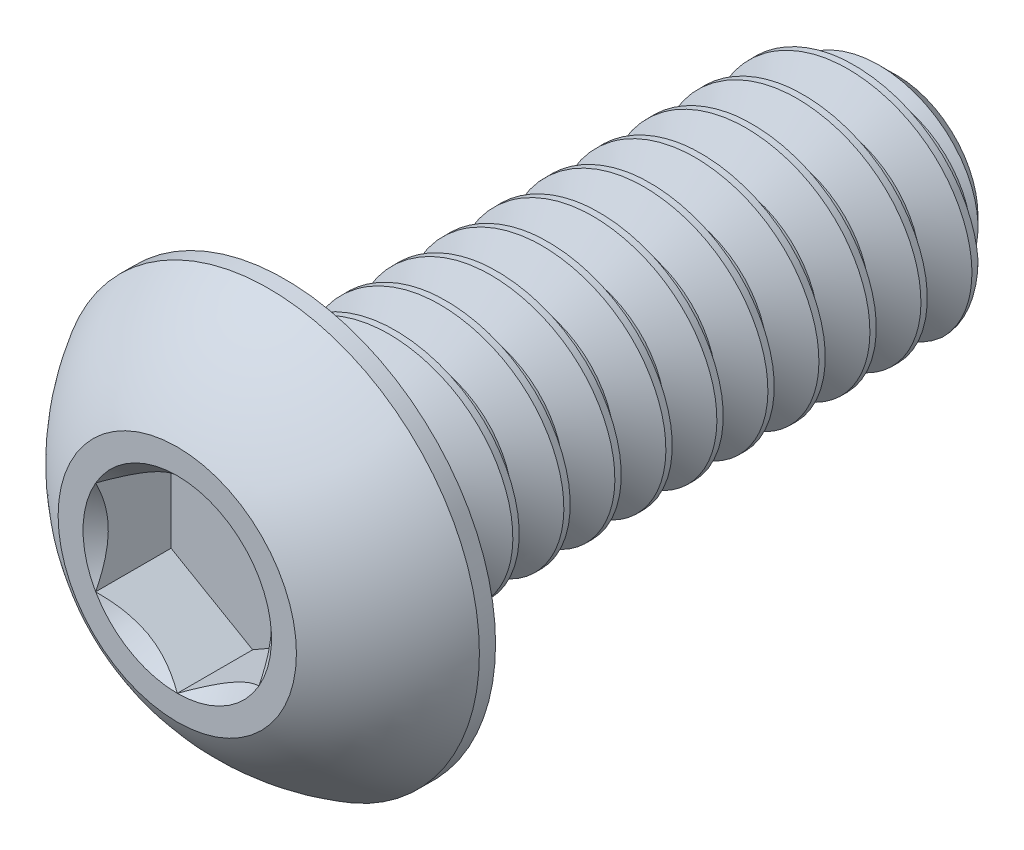
SolidWorks part; units mm, degrees
ref_plane "Front" through (0, 0, 0) normal (0, 0, 1) x (1, 0, 0)
ref_plane "Top" through (0, 0, 0) normal (0, 1, 0) x (1, 0, 0)
ref_plane "Right" through (0, 0, 0) normal (1, 0, 0) x (0, 0, -1)
sketch "Sketch1" plane through (0, 0, 0) normal (1, 0, 0) x (0, 0, -1)
  line L2 (0.8382, 0.9271) -> (5.6007, 0.9271)
  line L3 (5.6007, 0.9271) -> (5.6007, 0)
  line L4 (5.6007, 0) -> (0.8382, 0)
  line L6 (0.7125, 1.6383) -> (0.8382, 1.6383) construction
  line L7 (5.6007, 0.9271) -> (5.6007, -0.9271) construction
  line L8 (0, 0) -> (0.8382, 0) construction
  line L9 (0.8382, 1.6383) -> (0.8382, -1.6383) construction
  line L11 (0.8382, 0.9271) -> (0.8382, 0)
  line L13 (0, 0.635) -> (0, -0.635) construction
  line L14 (0, 0.635) -> (0, 0.9271) construction
  arc A3 (0, 0.9271) -> (0.7125, 1.6383) centre (1.6366, 0) cw construction
  dimension "D1" = 0.1257
revolve "Revolve1" add sketch "Sketch1" angle 360 mid plane about L4
sketch "Sketch3" plane through (0, 0, -5.6007) normal (0, 0, -1) x (-1, 0, 0)
  circle A0 centre (0, 0) radius 0.9271
curve "Helix/Spiral1" pitch 0.3969 height 5.1594 radius 0.9271 centre (0, 0, -5.6007) axis (0, 0, 1) start towards (0, 1, 0)
sketch "Sketch2" plane through (0, 0, 0) normal (1, 0, 0) x (0, 0, -1)
  line L0 (5.6007, 0.9271) -> (5.948, 0.9271)
  line L1 (5.948, 0.9271) -> (5.7991, 0.6693)
  line L2 (5.7991, 0.6693) -> (5.7495, 0.6693)
  line L3 (5.7495, 0.6693) -> (5.6007, 0.9271)
  line L4 (5.6751, 0.7982) -> (5.8736, 0.7982) construction
  dimension "D1" = 60
  dimension "D2" = 0.0496
  dimension "D3" = 0.1984
chamfer "Chamfer1" distance 0.2977 angle 45 1 edges at (0, 0.9271, -5.6007)
sweep "Cut-Sweep1" cut profiles "Sketch2" path "Helix/Spiral1"
sketch "Sketch7" plane through (0, 0, 0) normal (1, 0, 0) x (0, 0, -1)
  line L6 (0.7125, 1.6383) -> (0.8382, 1.6383) construction
  line L8 (0, 0) -> (0.8382, 0) construction
  line L11 (0.8382, 1.6383) -> (0.8382, -1.6383) construction
  line L12 (0.7125, 1.6383) -> (0.8382, 1.6383)
  line L13 (0, 0) -> (0.8382, 0)
  line L14 (0, 0.635) -> (0, -0.635) construction
  line L15 (0.8382, 1.6383) -> (0.8382, 0)
  line L16 (0, 0.9271) -> (0, 0)
  arc A2 (0.7125, 1.6383) -> (0, 0.9271) centre (1.6366, 0) ccw construction
  arc A3 (0.7125, 1.6383) -> (0, 0.9271) centre (1.6366, 0) ccw
revolve "Revolve2" add sketch "Sketch7" angle 360 mid plane about L13
sketch "Sketch5" plane through (0, 0, 0) normal (0, 0, 1) x (1, 0, 0)
  line L1 (0.635, -0.3666) -> (0.635, 0.3666)
  line L2 (0.635, 0.3666) -> (0, 0.7332)
  line L3 (0, 0.7332) -> (-0.635, 0.3666)
  line L4 (-0.635, 0.3666) -> (-0.635, -0.3666)
  line L5 (-0.635, -0.3666) -> (0, -0.7332)
  line L6 (0, -0.7332) -> (0.635, -0.3666)
  circle A0 centre (0, 0) radius 0.635 construction
extrude "Cut-Extrude2" cut sketch "Sketch5" against normal blind 0.5867
sketch "Sketch6" plane through (0, 0, 0) normal (0, 0, 1) x (1, 0, 0)
  circle A0 centre (0, 0) radius 0.7332
extrude "Cut-Extrude3" cut sketch "Sketch6" against normal blind 0.5867 draft 45
sketch "Sketch9" [suppressed] plane through (0, 0, -5.0546) normal (0, 0, 1) x (1, 0, 0)
  circle A2 centre (0, 0) radius 4.7625
extrude "Boss-Extrude2" [suppressed] add sketch "Sketch9" against normal offset from surface (19.05 mm away) 31.75 up to face at (0, 0.6294, -5.6007)
sketch "Sketch10" plane through (0, 0, 0) normal (1, 0, 0) x (0, 0, -1)
  line L0 (5.6007, 0.9271) -> (5.6007, -0.9271) construction
  point P0 (5.0054, -0.9271)
  dimension "D1" = 0.5953
equation "\"D3@Helix/Spiral1\" = \"Lg@Sketch1\" + \"D4@Helix/Spiral1\""
equation "\"D2@Sketch2\" = \"D4@Helix/Spiral1\" * .125"
equation "\"D3@Sketch2\" = \"D4@Helix/Spiral1\" * .5"
equation "\"D1@Chamfer1\" = \"D4@Helix/Spiral1\" * .75"
equation "\"D1@Cut-Extrude2\" = \"Head Ht@Sketch1\" * .7"
equation "\"D1@Sketch1\" = \"Head Ht@Sketch1\" * .15"
equation "\"D1@Sketch10\" = \"D4@Helix/Spiral1\" * 1.5"
equation "\"D1@Cut-Extrude3\" = \"D1@Cut-Extrude2\""
